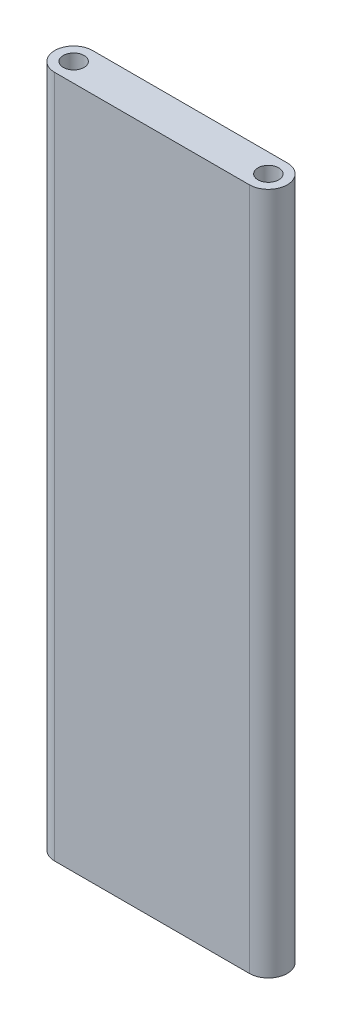
SolidWorks part; units mm, degrees
ref_plane "Front Plane" through (0, 0, 0) normal (0, 0, 1) x (1, 0, 0)
ref_plane "Top Plane" through (0, 0, 0) normal (0, 1, 0) x (1, 0, 0)
ref_plane "Right Plane" through (0, 0, 0) normal (1, 0, 0) x (0, 0, -1)
sketch "Sketch1" plane through (0, 0, 0) normal (0, 1, 0) x (1, 0, 0)
  line L0 (-28.5, 0) -> (28.5, 0) construction
  line L1 (-28.5, 0) -> (28.5, 0) construction
  line L2 (-28.5, 5.55) -> (28.5, 5.55)
  line L3 (-28.5, -5.55) -> (28.5, -5.55)
  circle A0 centre (-28.5, 0) radius 3.05
  circle A1 centre (28.5, 0) radius 3.05
  arc A2 (-28.5, 5.55) -> (-28.5, -5.55) centre (-28.5, 0) ccw
  arc A3 (28.5, -5.55) -> (28.5, 5.55) centre (28.5, 0) ccw
  point P4 (0, 0)
  point P9 (0, 0)
  point P10 (25.1139, 0)
  dimension "D1" = 6.1
  dimension "D2" = 2.5
  dimension "D3" = 57
extrude "Boss-Extrude1" add sketch "Sketch1" along normal mid plane 200
